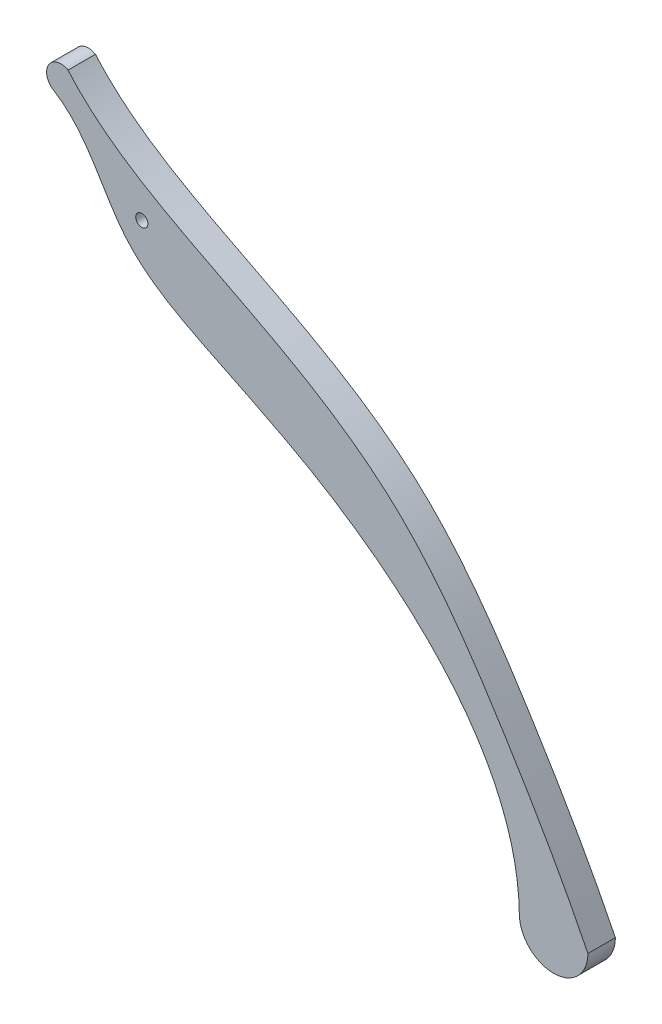
SolidWorks part; units mm, degrees
ref_plane "Plan de face" through (0, 0, 0) normal (0, 0, 1) x (1, 0, 0)
ref_plane "Plan de dessus" through (0, 0, 0) normal (0, 1, 0) x (1, 0, 0)
ref_plane "Plan de droite" through (0, 0, 0) normal (1, 0, 0) x (0, 0, -1)
sketch "Esquisse1" plane through (0, 0, 0) normal (0, 0, 1) x (1, 0, 0)
  line L0 (0, 0) -> (-35.3553, 35.3553) construction
  line L1 (0, 0) -> (180, -180) construction
  line L2 (-38.4803, 29.9427) -> (-32.2303, 40.768) construction
  line L3 (55, 0) -> (-55, 0) construction
  line L4 (-6.25, -10.8253) -> (6.25, 10.8253) construction
  circle A0 centre (0, 0) radius 12.5 construction
  arc A8 (165, -180) -> (195, -180) centre (180, -180) ccw
  circle A11 centre (0, 0) radius 2.65
  arc A12 (-32.2303, 40.768) -> (-38.4803, 29.9427) centre (-35.3553, 35.3553) ccw
  spline S0 degree 3 poles (-32.2303, 40.768) (-21.4871, 28.2858) (6.8174, 8.9856) (57.9076, -15.3354) (116.0007, -50.55) (158.2502, -113.4101) (183.8116, -157.3423) (195, -180) knots 0 0 0 0 0.150864 0.313676 0.525225 0.76792 1 1 1 1
  spline S1 degree 3 poles (-38.4803, 29.9427) (-23.0028, 20.3955) (-12.9306, -13.408) (30.6191, -35.6844) (67.1256, -53.0095) (125.3849, -89.8354) (164.4807, -135.2235) (165, -180) knots 0 0 0 0 0.172046 0.317203 0.462334 0.575673 1 1 1 1
  point P4 (171.3558, -139.5689)
  point P6 (151.4829, -99.5708)
  point P14 (0, 0)
  point P15 (-35.3553, 35.3553)
  point P18 (0, 0)
  point P22 (161.7604, -143.4365)
  point P26 (135.9804, -101.4118)
  point P29 (157.9254, -139.5689)
  point P32 (18.7183, -27.9767)
  point P34 (68.1661, -49.3344)
  point P35 (13.6886, -22.0541)
  point P37 (54.0839, -40.2845)
  point P38 (-22.9638, 14.1111)
  point P39 (166.9628, -129.4847)
  point P40 (158.054, -143.9641)
  point P41 (143.3548, -114.7099)
  point P42 (152.4337, -132.4354)
  point P43 (0, 0)
  point P44 (156.1867, -141.0934)
  point P45 (146.5755, -121.1591)
  point P46 (154.4068, -137.8896)
  point P47 (52.726, -43.1992)
  point P48 (23.9168, -27.7966)
  point P49 (51.2142, -41.0989)
  point P50 (24.8868, -31.1222)
  point P51 (54.2626, -45.533)
  point P52 (115.8783, -90.0176)
  point P53 (75.6244, -58.2726)
  point P54 (70.3517, -22.6416)
  point P55 (109.8579, -52.1735)
  point P56 (52.9455, -13.8407)
  point P57 (168.3823, -129.994)
  point P58 (149.7871, -132.1481)
  point P59 (112.6284, -83.4718)
  point P60 (157.9459, -114.4993)
  point P61 (174.3324, -141.6191)
  point P62 (30.3494, -35.304)
  point P63 (69.5837, -55.2714)
  point P64 (99.8852, -75.0638)
  point P65 (156.1542, -140.0695)
  point P66 (98.5487, -73.7909)
  dimension "D1" = 25
  dimension "D2" = 12.5
  dimension "D3" = 30
  dimension "D9" = 5.3
  dimension "D4" = 50
  dimension "D5" = 254.5584
  dimension "D6" = 45
  dimension "D7" = 180
  dimension "D8" = 60
extrude "Boss.-Extru.1" add sketch "Esquisse1" along normal blind 12
